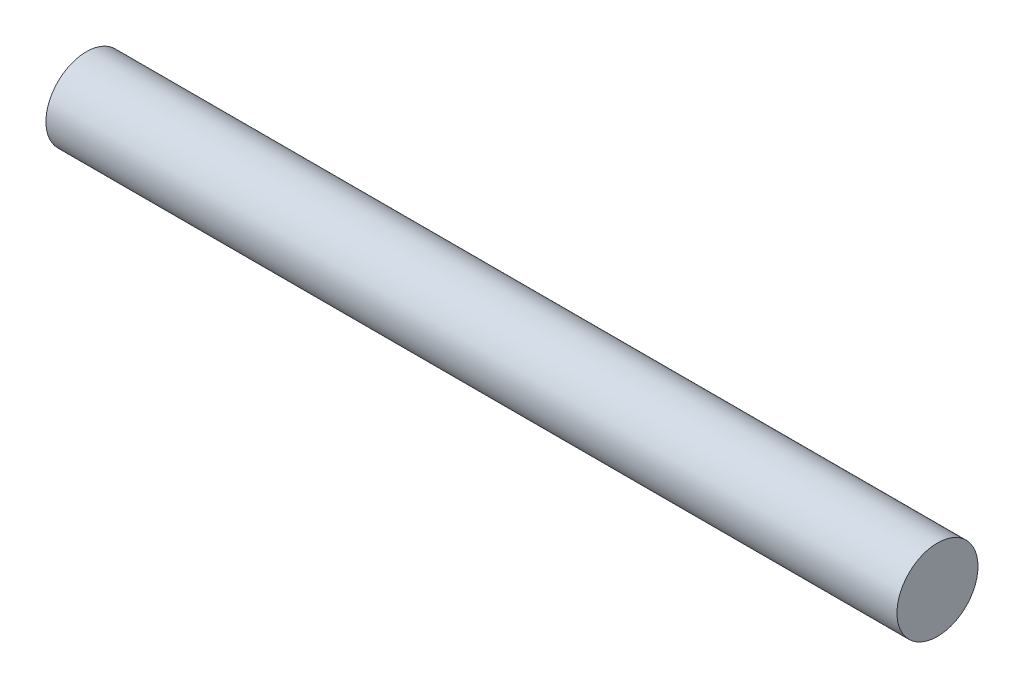
SolidWorks part; units mm, degrees
material "AISI Type A2 Tool Steel"
ref_plane "Front Plane" through (0, 0, 0) normal (0, 0, 1) x (1, 0, 0)
ref_plane "Top Plane" through (0, 0, 0) normal (0, 1, 0) x (1, 0, 0)
ref_plane "Right Plane" through (0, 0, 0) normal (1, 0, 0) x (0, 0, -1)
other "Bounding Box"
ref_plane "Default Plane" through (-8.9266, -12.7485, 0) normal (-0.1736, 0.9848, 0) x (0.9848, 0.1736, 0)
sketch "Sketch2" plane through (0, 0, 0) normal (1, 0, 0) x (0, 0, -1)
  circle A0 centre (0, 0) radius 6.35
  dimension "D1" = 12.7
extrude "Boss-Extrude1" add sketch "Sketch2" along normal mid plane 133.35
